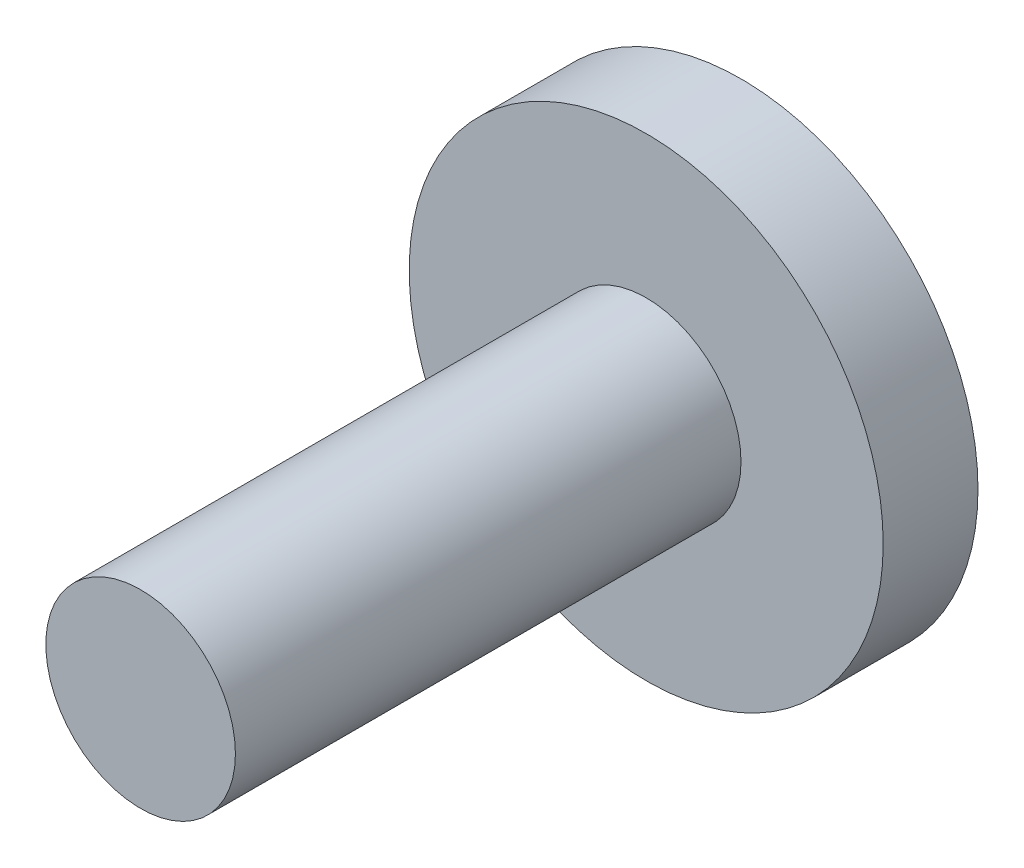
SolidWorks part; units mm, degrees
ref_plane "Front Plane" through (0, 0, 0) normal (0, 0, 1) x (1, 0, 0)
ref_plane "Top Plane" through (0, 0, 0) normal (0, 1, 0) x (1, 0, 0)
ref_plane "Right Plane" through (0, 0, 0) normal (1, 0, 0) x (0, 0, -1)
sketch "Sketch1" plane through (0, 0, 0) normal (0, 0, 1) x (1, 0, 0)
  circle A0 centre (0, 0) radius 3
  circle A1 centre (0, 0) radius 7.5
  dimension "D1" = 6
  dimension "D2" = 15
extrude "Boss-Extrude1" add sketch "Sketch1" along normal blind 19 contours A0 region at (0, 0, 0)
extrude "Boss-Extrude2" add sketch "Sketch1<3>" along normal blind 3
sketch "Sketch1<3>" plane through (0, 0, 0) normal (0, 0, 1) x (1, 0, 0) same geometry as "Sketch1"
